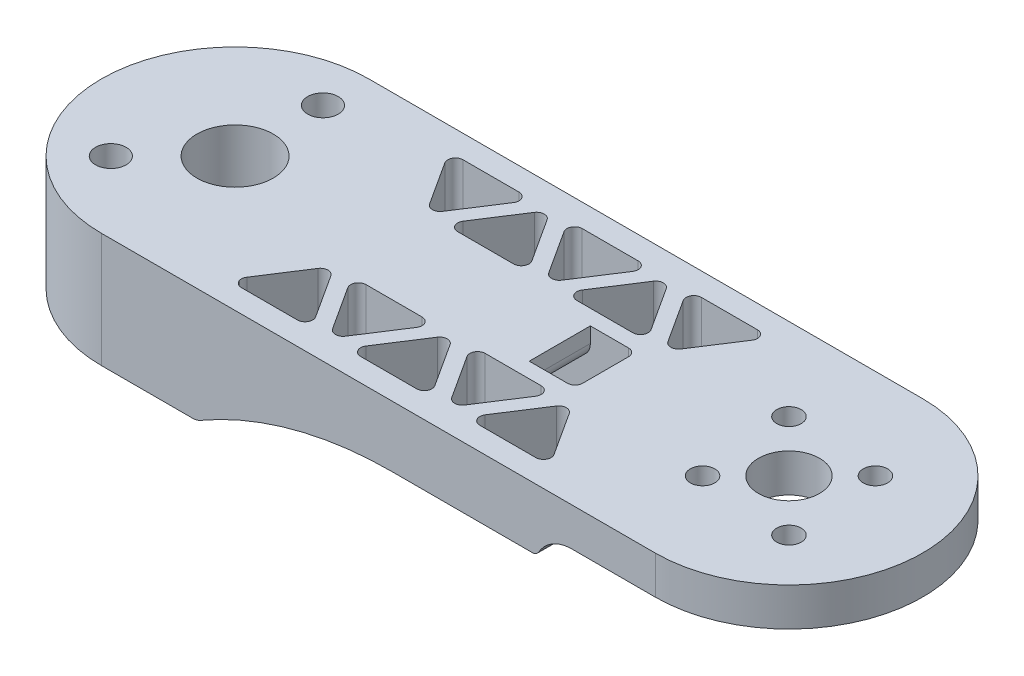
SolidWorks part; units mm, degrees
material "PLA"
ref_plane "Front" through (0, 0, 0) normal (0, 0, 1) x (1, 0, 0)
ref_plane "Top" through (0, 0, 0) normal (0, 1, 0) x (1, 0, 0)
ref_plane "Right" through (0, 0, 0) normal (1, 0, 0) x (0, 0, -1)
sketch "Skizze1" plane through (0, 0, 0) normal (0, 0, 1) x (1, 0, 0)
  line L0 (-15, 0) -> (15, 0)
  line L2 (15, 7) -> (92.5, 7)
  line L3 (92.5, 7) -> (92.5, 15)
  line L4 (92.5, 15) -> (-15, 15)
  line L5 (-15, 15) -> (-15, 0)
  line L6 (0, 0) -> (0, 81.75) construction
  line L7 (75, 15) -> (75, -2.625) construction
  line L8 (15, 7) -> (15, 0)
  dimension "D1" = 30
  dimension "D2" = 15
  dimension "D3" = 75
  dimension "D4" = 17.5
  dimension "D5" = 8
extrude "Aufsatz-Linear austragen1" add sketch "Skizze1" along normal blind 35
sketch "Skizze2" plane through (0, 15, 0) normal (0, 1, 0) x (1, 0, 0)
  line L0 (92.5, -35) -> (-15, -35) construction
  line L1 (92.5, 0) -> (-15, 0) construction
  line L2 (92.5, -35) -> (75, -35)
  line L3 (-15, -17.5) -> (134.1131, -17.5) construction
  line L4 (-15, -35) -> (-15, 0) construction
  line L5 (92.5, -35) -> (92.5, 0) construction
  line L6 (92.5, -35) -> (92.5, 0)
  line L7 (92.5, 0) -> (75, 0)
  arc A0 (75, -35) -> (75, 0) centre (75, -17.5) ccw
  line M1 (92.5, 0) -> (-15, 0)
  line M3 (-15, -35) -> (92.5, -35)
  line M4 (92.5, -35) -> (92.5, 0)
  dimension "D1" = 35
extrude "Schnitt-Linear austragen1" cut sketch "Skizze2" against normal up to surface (8 mm away) contours A0 L6 M1 | A0 M3 M4 region at (88.5911, 15, 3.9089) region at (88.5911, 15, 31.0911) up to face at (53.75, 7, 17.5)
fillet "Verrundung1" radius 50 1 edges at (15, 7, 17.5)
sketch "Skizze3" plane through (0, 15, 0) normal (0, 1, 0) x (1, 0, 0)
  line L0 (68.2825, -10.7825) -> (81.7175, -24.2175) construction
  line L2 (69.3431, -23.1569) -> (80.6569, -11.8431) construction
  line L3 (75, -17.5) -> (87.189, -17.5) construction
  circle A0 centre (75, -17.5) radius 8 construction
  arc A1 (75, -35) -> (75, 0) centre (75, -17.5) ccw construction
  circle A2 centre (75, -17.5) radius 9.5 construction
  circle A7 centre (68.2825, -10.7825) radius 1.6
  circle A8 centre (81.7175, -24.2175) radius 1.6
  circle A9 centre (80.6569, -11.8431) radius 1.6
  circle A10 centre (69.3431, -23.1569) radius 1.6
  circle A11 centre (75, -17.5) radius 4
  dimension "D1" = 16
  dimension "D2" = 19
  dimension "D3" = 3.2
  dimension "D4" = 45
  dimension "D6" = 8
  dimension "D5" = 90
extrude "Schnitt-Linear austragen2" cut sketch "Skizze3" against normal up to surface (8 mm away) up to face at (62.1324, 7, 17.5)
sketch "Skizze5" plane through (0, 15, 0) normal (0, 1, 0) x (1, 0, 0)
  line L0 (75, -17.5) -> (75, 0) construction
  line L1 (34.4902, -17.5) -> (87.8321, -17.5) construction
  line L2 (75, 0) -> (-15, 0) construction
  line L10 (45, -13.5) -> (51, -13.5)
  line L11 (45, -13.5) -> (45, -21.5)
  line L12 (45, -21.5) -> (51, -21.5)
  line L13 (51, -13.5) -> (51, -21.5)
  dimension "D1" = 17.5
  dimension "D4" = 8
  dimension "D3" = 6
  dimension "D2" = 24
extrude "Schnitt-Linear austragen9" cut sketch "Skizze5" against normal through all and the other way through all
ref_plane "Ebene1" through (0, 0, 17.5) normal (0, 0, -1) x (-1, 0, 0)
sketch "Skizze6" plane through (0, 15, 0) normal (0, 1, 0) x (1, 0, 0)
  line L0 (-15, -35) -> (-15, 0) construction
  line L1 (75, -35) -> (-15, -35) construction
  circle A0 centre (2.5, -17.5) radius 5
  dimension "D1" = 10
  dimension "D2" = 17.5
  dimension "D3" = 17.5
extrude "Schnitt-Linear austragen5" cut sketch "Skizze6" against normal up to surface (15 mm away) up to face at (0, 0, 17.5)
sketch "Skizze13" plane through (0, 7, 0) normal (0, -1, 0) x (1, 0, 0)
  line L0 (59.5, 0) -> (59.5, 35)
  line L1 (75, 0) -> (-15, 0) construction
  line L2 (75, 35) -> (-15, 35) construction
  line L3 (59.5, 35) -> (75, 35)
  line L4 (59.5, 0) -> (75, 0)
  arc A0 (75, 0) -> (75, 35) centre (75, 17.5) ccw
  point P1 (92.5, 17.5)
  dimension "D1" = 33
extrude "Schnitt-Linear austragen14" cut sketch "Skizze13" against normal blind 3
sketch "Skizze7" plane through (0, 15, 0) normal (0, 1, 0) x (1, 0, 0)
  line L0 (75, 0) -> (-15, 0) construction
  line L1 (-15, -35) -> (-15, 0) construction
  line L2 (75, -35) -> (-15, -35) construction
  circle A0 centre (-10, -5) radius 2
  circle A1 centre (-10, -30) radius 2
  dimension "D1" = 4
  dimension "D2" = 5
  dimension "D3" = 5
  dimension "D4" = 5
sketch "Skizze9" plane through (0, 15, 0) normal (0, 1, 0) x (1, 0, 0)
  line L3 (-15, -17.5) -> (141.5782, -17.5) construction
  line L4 (-15, -35) -> (-15, 0) construction
  line L29 (16, -3) -> (21.5, -11.5)
  line L30 (21.5, -11.5) -> (27, -3)
  line L31 (27, -3) -> (16, -3)
  line L32 (29.3, -3) -> (23.8, -11.5)
  line L33 (23.8, -11.5) -> (34.8, -11.5)
  line L34 (34.8, -11.5) -> (29.3, -3)
  line L35 (11.7965, -3) -> (16.6225, -3) construction
  line L36 (75, 0) -> (-15, 0) construction
  line L37 (11.7965, -32) -> (16.6225, -32) construction
  line L38 (34.8, -23.5) -> (29.3, -32)
  line L39 (23.8, -23.5) -> (34.8, -23.5)
  line L40 (29.3, -32) -> (23.8, -23.5)
  line L41 (27, -32) -> (16, -32)
  line L42 (21.5, -23.5) -> (27, -32)
  line L43 (16, -32) -> (21.5, -23.5)
  dimension "D1" = 3
  dimension "D2" = 11
  dimension "D3" = 31
  dimension "D4" = 2.3
  dimension "D5" = 12
extrude "Materialwegnahme 3D Druck" cut sketch "Skizze9" against normal through all both and the other way through all
pattern_linear "Lineares Muster1" count 2 spacing 15.6 along (1, 0, 0) of "Materialwegnahme 3D Druck"
fillet "Verrundung9" radius 17.5 2 edges at (-15, 7.5, 35) (-15, 7.5, 0)
ref_plane "Ebene2" through (0, 0, 17.5) normal (0, 0, -1) x (-1, 0, 0)
sketch "Skizze14" plane through (0, 0, 17.5) normal (0, 0, -1) x (-1, 0, 0)
  line L0 (-40.5147, 7) -> (-59.5, 7) construction
  line L1 (-40.5147, 7) -> (-51, 7)
  line L2 (-51, 7) -> (-51, 11)
  line L3 (-40.5147, 11) -> (-51, 11)
  line L4 (-15, 0) -> (-9, 0)
  line L6 (-9, 4) -> (-13.9252, 4)
  line L7 (-9, 4) -> (-9, 0)
  line L8 (-51, 7) -> (-51, 15) construction
  line L9 (-51, 7) -> (-51, 15) construction
  arc A0 (-15, 0) -> (-40.5147, 7) centre (-40.5147, -43) ccw construction
  arc A1 (-15, 0) -> (-40.5147, 7) centre (-40.5147, -43) ccw
  arc A2 (-13.9252, 4) -> (-40.5147, 11) centre (-40.5147, -43) ccw
  dimension "D1" = 4
  dimension "D2" = 4
  dimension "D3" = 6
extrude "Schnitt-Linear austragen15" cut sketch "Skizze14" against normal mid plane 8
sketch "Skizze19" plane through (0, 15, 0) normal (0, 1, 0) x (1, 0, 0)
  line L0 (47.2, -32) -> (58.2, -32)
  line L1 (58.2, -32) -> (52.7, -23.5)
  line L2 (52.7, -23.5) -> (47.2, -32)
  line L3 (50.4, -23.5) -> (44.9, -32) construction
  line L4 (39.4, -23.5) -> (50.4, -23.5) construction
  line L5 (51, -17.5) -> (58.685, -17.5) construction
  line L6 (51, -13.5) -> (51, -21.5) construction
  line L7 (58.2, -3) -> (52.7, -11.5)
  line L8 (52.7, -11.5) -> (47.2, -3)
  line L9 (47.2, -3) -> (58.2, -3)
  dimension "D1" = 2.3
extrude "Schnitt-Linear austragen19" cut sketch "Skizze19" against normal through all both and the other way through all
fillet "Verrundung10" radius 2 2 edges at (13.9252, 4, 17.5) (45, 11, 17.5)
fillet "Verrundung12" radius 2 2 edges at (15, 0, 6.75) (15, 0, 28.25)
fillet "Verrundung13" radius 5 1 edges at (59.5, 10, 17.5)
fillet "Verrundung14" radius 1 1 edges at (59.5, 7, 17.5)
fillet "Verrundung16" radius 1 32 edges at (16, 7.7889, 32) (21.5, 9.1216, 23.5) (27, 10.0694, 32) (23.8, 9.5617, 11.5) (21.5, 9.1216, 11.5) (23.8, 9.5617, 23.5) (29.3, 10.363, 32) (31.6, 10.5994, 32) (29.3, 10.363, 3) (37.1, 10.9416, 23.5) (44.9, 11, 32) (39.4, 10.9938, 23.5) (47.2, 11, 32) (44.9, 11, 3) (39.4, 10.9938, 11.5) (37.1, 10.9416, 11.5) (52.7, 11, 11.5) (16, 7.7889, 3) (31.6, 10.5994, 3) (47.2, 11, 3) (52.7, 11, 23.5) (58.2, 11, 3) (34.8, 10.8362, 11.5) (50.4, 11, 11.5) (42.6, 11, 32) (58.2, 11, 32) (51, 11, 21.5) (51, 11, 13.5) (50.4, 11, 23.5) (42.6, 11, 3) (27, 10.0694, 3) (34.8, 10.8362, 23.5)
fillet "Verrundung17" radius 2 2 edges at (9, 2, 21.5) (9, 2, 13.5)
sketch "Skizze25" plane through (0, 0, 0) normal (0, -1, 0) x (1, 0, 0)
  line L0 (2.5, 0) -> (14.4571, 0) construction
  line L1 (2.5, 0) -> (9, 0)
  line L2 (9, 0) -> (9, 13.5)
  line L3 (6.2749, 13.5) -> (9, 13.5)
  line L4 (2.5, 8.4) -> (2.5, 12)
  line L5 (-1, 0.3536) -> (-1, 8.4)
  line L6 (-1, 8.4) -> (2.5, 8.4)
  circle A0 centre (2.5, 17.5) radius 5 construction
  arc A1 (-15, 17.5) -> (2.5, 0) centre (2.5, 17.5) ccw construction
  arc A3 (-1, 0.3536) -> (2.5, 0) centre (2.5, 17.5) ccw
  arc A5 (2.5, 12) -> (6.2749, 13.5) centre (2.5, 17.5) ccw
  dimension "D4" = 13.5
  dimension "D5" = 11
  dimension "D1" = 3.6
  dimension "D2" = 3.5
  dimension "D3" = 10
extrude "Aufsatz-Linear austragen2" add sketch "Skizze25" along normal blind 2.5
sketch "Skizze23" plane through (0, 15, 0) normal (0, 1, 0) x (1, 0, 0)
  line L0 (2.5, 0) -> (2.5, -17.5) construction
  line L1 (2.5, -17.5) -> (-9.8744, -29.8744) construction
  circle A0 centre (2.5, -6) radius 2
  arc A1 (-15, -17.5) -> (2.5, -35) centre (2.5, -17.5) ccw construction
  circle A2 centre (-5.6317, -25.6317) radius 2
  dimension "D1" = 4
  dimension "D4" = 6
  dimension "D2" = 6
  dimension "D3" = 135
extrude "Schnitt-Linear austragen20" cut sketch "Skizze23" against normal through all both and the other way through all
fillet "Verrundung18" radius 2 3 edges at (9, -1.25, 0) (-1, -1.25, 0.3536) (-1, -1.25, 8.4)
fillet "Verrundung19" radius 0.5 4 edges at (6.2749, -1.25, 13.5) (9, -1.25, 13.5) (2.5, -1.25, 12) (2.5, -1.25, 8.4)
